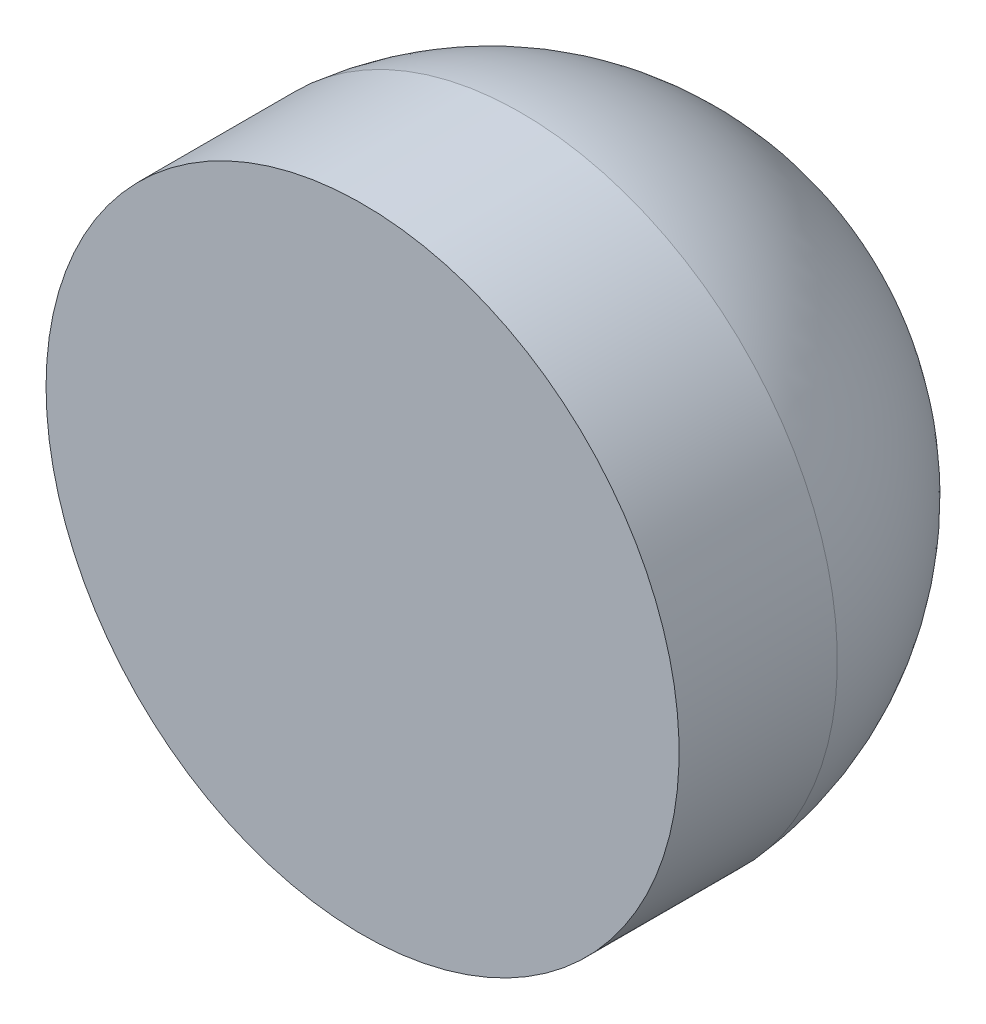
SolidWorks part; units mm, degrees
ref_plane "Front Plane" through (0, 0, 0) normal (0, 0, 1) x (1, 0, 0)
ref_plane "Top Plane" through (0, 0, 0) normal (0, 1, 0) x (1, 0, 0)
ref_plane "Right Plane" through (0, 0, 0) normal (1, 0, 0) x (0, 0, -1)
sketch "Sketch4" plane through (0, 0, 0) normal (0, 1, 0) x (1, 0, 0)
  line L0 (0, 5.9) -> (2.5, 5.9)
  line L1 (2.5, 5.9) -> (2.5, 7.9)
  line L2 (0, 5.9) -> (0, 0)
  line L3 (0, 0) -> (6, 0)
  line L4 (6, 0) -> (6, 3)
  arc A0 (2.5, 7.9) -> (6, 3) centre (0.0268, 2.4334) cw
  point P7 (0, 0)
  point P8 (0, 0)
  point P9 (0, 0)
  point P11 (0, 0)
  point P12 (0, 0)
  point P13 (0, 0)
  point P14 (0, 0)
  point P15 (0, 0)
  point P16 (0, 0)
  point P17 (0, 0)
  point P18 (0, 0)
  point P19 (4.9092, 5.9209)
  point P20 (0, 0)
  dimension "D1" = 6
  dimension "D2" = 3
  dimension "D3" = 5.9
  dimension "D4" = 2
  dimension "D5" = 2.5
  dimension "D6" = 6
revolve "Revolve1" add sketch "Sketch4" angle 360 about L2
